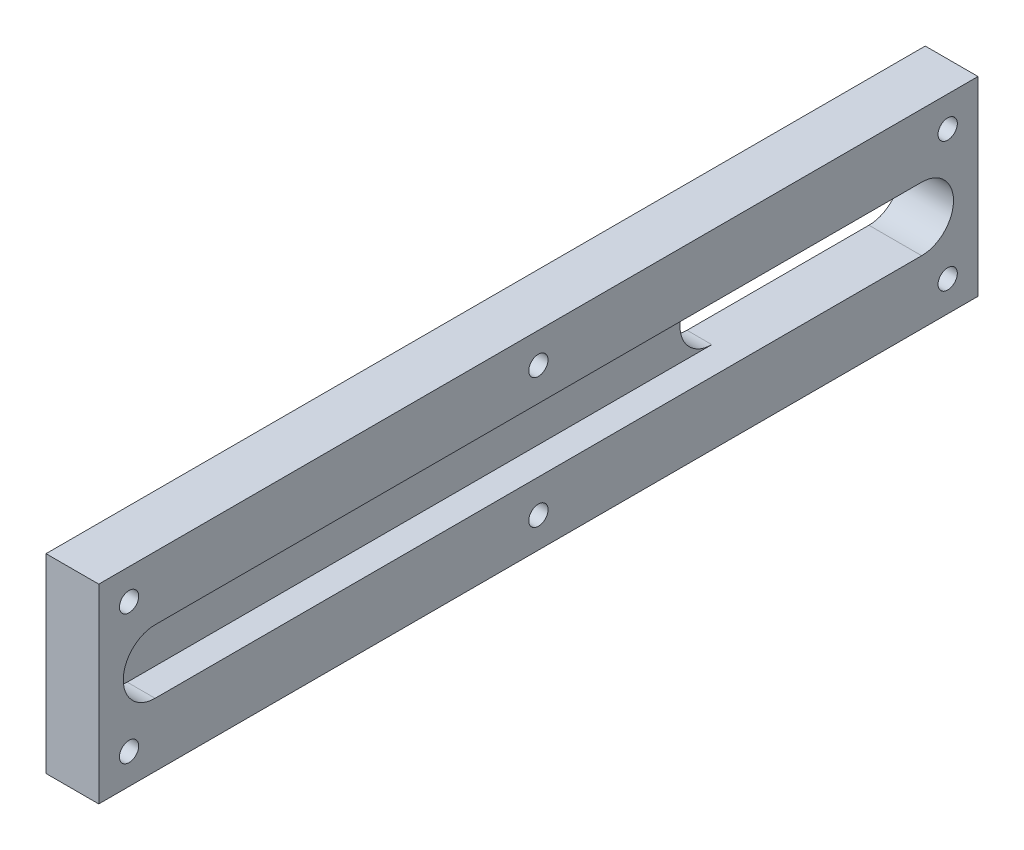
SolidWorks part; units mm, degrees
material "Delrin 2700 NC010, Low Viscosity Acetal Copolymer (SS)"
ref_plane "Front" through (0, 0, 0) normal (0, 0, 1) x (1, 0, 0)
ref_plane "Top" through (0, 0, 0) normal (0, 1, 0) x (1, 0, 0)
ref_plane "Right" through (0, 0, 0) normal (1, 0, 0) x (0, 0, -1)
sketch "Sketch1" plane through (0, 0, 0) normal (1, 0, 0) x (0, 0, -1)
  line L0 (-80.2752, 0) -> (80.2752, 0) construction
  line L1 (92.075, -19.939) -> (-92.075, -19.939)
  line L2 (92.075, -19.939) -> (92.075, 19.939)
  line L3 (92.075, 19.939) -> (-92.075, 19.939)
  line L4 (-92.075, -19.939) -> (-92.075, 19.939)
  line L5 (92.075, -19.939) -> (-92.075, 19.939) construction
  line L6 (92.075, 19.939) -> (-92.075, -19.939) construction
  line L7 (-80.2752, 6.6675) -> (80.2752, 6.6675)
  line L8 (-80.2752, -6.6675) -> (80.2752, -6.6675)
  arc A0 (-80.2752, 6.6675) -> (-80.2752, -6.6675) centre (-80.2752, 0) ccw
  arc A1 (80.2752, -6.6675) -> (80.2752, 6.6675) centre (80.2752, 0) ccw
  point P0 (0, 0)
  point P8 (0, 0)
  dimension "D4" = 13.335
  dimension "D1" = 160.5505
  dimension "D2" = 184.15
  dimension "D3" = 39.878
extrude "Boss-Extrude1" add sketch "Sketch1" along normal blind 11.049
hole_wizard "#10-32 Tapped Hole1" positions "Sketch3" profile "Sketch4" tap size "#10-32" standard "ANSI Inch" end condition through all
sketch "Sketch3" plane through (11.049, 0, 0) normal (1, 0, 0) x (0, 0, -1)
  line L0 (-85.725, 13.589) -> (0, 13.589) construction
  line L1 (0, 13.589) -> (85.725, 13.589) construction
  line L3 (-85.725, 19.939) -> (-85.725, 13.589) construction
  line L4 (92.075, 19.939) -> (-92.075, 19.939) construction
  line L5 (-85.725, 13.589) -> (-85.725, -13.589) construction
  line L6 (-85.725, -13.589) -> (-85.725, -19.939) construction
  line L7 (-92.075, -19.939) -> (92.075, -19.939) construction
  line L8 (-92.075, 19.939) -> (-92.075, -19.939) construction
  point P0 (-85.725, 13.589)
  point P2 (-85.725, -13.589)
  point P4 (0, -13.589)
  point P6 (85.725, -13.589)
  point P8 (85.725, 13.589)
  point P10 (0, 13.589)
  dimension "D1" = 6.35
  dimension "D2" = 6.35
sketch "Sketch4" plane through (11.049, 13.589, 85.725) normal (0, 1, 0) x (0, 0, -1)
  line L0 (0, 0) -> (0, 11.049)
  line L1 (0, 11.049) -> (2.0193, 11.049)
  line L2 (2.0193, 11.049) -> (2.0193, 0)
  line L5 (2.0193, 0) -> (0, 0)
  line L11 (0, -6.35) -> (0, 107.95) construction
  dimension "Thru Tap Drill Dia." = 4.0386
  dimension "Thru Tap Drill Depth" = 11.049
cosmetic thread "Hole Thread1" parameters "D2"=4.826
cosmetic thread "Hole Thread2" parameters "D2"=4.826
cosmetic thread "Hole Thread3" parameters "D2"=4.826
cosmetic thread "Hole Thread4" parameters "D2"=4.826
cosmetic thread "Hole Thread5" parameters "D2"=4.826
cosmetic thread "Hole Thread6" parameters "D2"=4.826
sketch "Sketch5" plane through (0, 0, 0) normal (-1, 0, 0) x (0, 0, 1)
  line L6 (-80.2752, -6.6675) -> (80.2752, -6.6675)
  line L7 (80.2752, 6.6675) -> (-80.2752, 6.6675)
  line L8 (-42.1752, -6.6675) -> (80.2752, -6.6675)
  line L9 (80.2752, 6.6675) -> (-42.1752, 6.6675)
  arc A2 (-42.1752, 6.6675) -> (-42.1752, -6.6675) centre (-42.1752, 0) cw
  arc A6 (-80.2752, 6.6675) -> (-80.2752, -6.6675) centre (-80.2752, 0) ccw construction
  arc A7 (80.2752, -6.6675) -> (80.2752, 6.6675) centre (80.2752, 0) ccw
  arc A8 (-80.2752, 6.6675) -> (-80.2752, -6.6675) centre (-80.2752, 0) ccw
  arc A9 (80.2752, -6.6675) -> (80.2752, 6.6675) centre (80.2752, 0) ccw
  dimension "D2" = 38.1
  dimension "D1" = 0
extrude "Boss-Extrude2" add sketch "Sketch5" against normal blind 5.207
